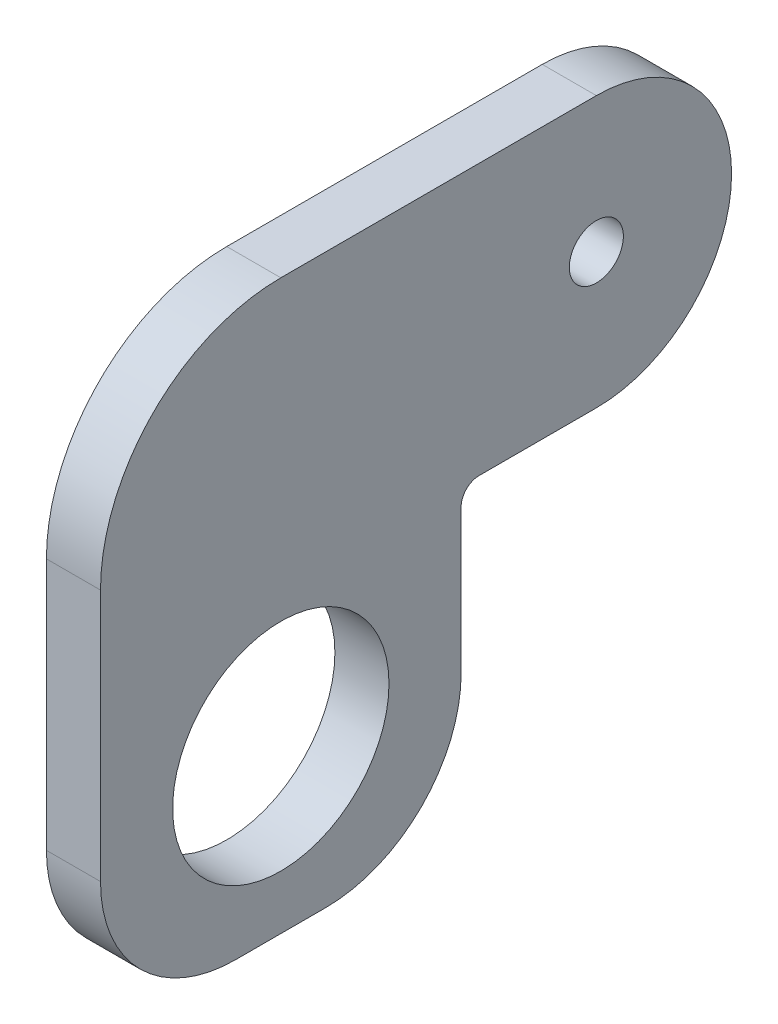
SolidWorks part; units mm, degrees
ref_plane "Front Plane" through (0, 0, 0) normal (0, 0, 1) x (1, 0, 0)
ref_plane "Top Plane" through (0, 0, 0) normal (0, 1, 0) x (1, 0, 0)
ref_plane "Right Plane" through (0, 0, 0) normal (1, 0, 0) x (0, 0, -1)
sketch "Sketch1" plane through (0, 0, 0) normal (1, 0, 0) x (0, 0, -1)
  line L1 (-7.5, 7.5) -> (7.5, 7.5) construction
  line L2 (-7.5, 7.5) -> (-7.5, -7.5) construction
  line L3 (-7.5, -7.5) -> (7.5, -7.5) construction
  line L4 (7.5, 7.5) -> (7.5, -7.5) construction
  line L5 (-7.5, 7.5) -> (7.5, -7.5) construction
  line L6 (-7.5, -7.5) -> (7.5, 7.5) construction
  line L7 (-7.5, 7.5) -> (7.5, 7.5)
  line L9 (-27.5, -9) -> (-27.5, 12.5)
  line L10 (-17.5, 22.5) -> (7.5, 22.5)
  line L11 (7.5, 22.5) -> (7.5, 7.5)
  line L12 (-27.5, -9) -> (-7.5, -9)
  line L13 (-7.5, -9) -> (-7.5, 7.5)
  line L14 (-7.5, 7.5) -> (7.5, 22.5) construction
  circle A0 centre (-17.5, 0) radius 6
  circle A1 centre (-17.5, 0) radius 9 construction
  circle A2 centre (0, 15) radius 1.5
  arc A3 (-27.5, 12.5) -> (-17.5, 22.5) centre (-17.5, 12.5) cw
  point P0 (0, 0)
  point P15 (-17.5, -9)
  dimension "D4" = 12
  dimension "D5" = 3
  dimension "D6" = 3
  dimension "D7" = 10
  dimension "D1" = 15
  dimension "D2" = 15
  dimension "D3" = 20
extrude "Boss-Extrude1" add sketch "Sketch1" along normal mid plane 3
fillet "Fillet1" radius 7.5 4 edges at (0, -9, 27.5) (0, -9, 7.5) (0, 7.5, -7.5) (0, 22.5, -7.5)
fillet "Fillet2" radius 1 1 edges at (0, 7.5, 7.5)
